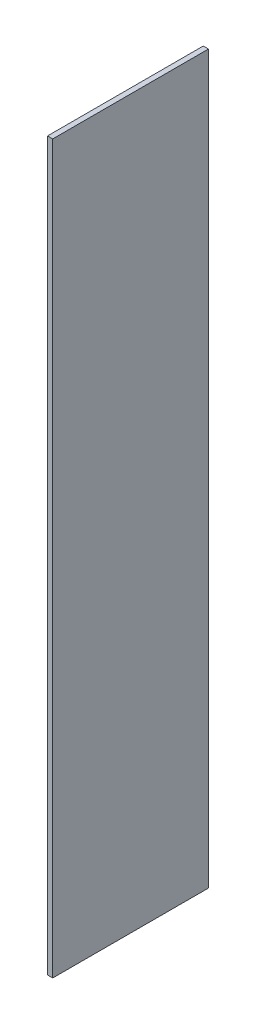
SolidWorks part; units mm, degrees
ref_plane "Front Plane" through (0, 0, 0) normal (0, 0, 1) x (1, 0, 0)
ref_plane "Top Plane" through (0, 0, 0) normal (0, 1, 0) x (1, 0, 0)
ref_plane "Right Plane" through (0, 0, 0) normal (1, 0, 0) x (0, 0, -1)
sketch "Sketch1" plane through (0, 0, 0) normal (0, 0, 1) x (1, 0, 0)
  line L1 (0, 0) -> (0.1, 0)
  line L2 (0, 0) -> (0, 14)
  line L3 (0, 14) -> (0.1, 14)
  line L4 (0.1, 0) -> (0.1, 14)
  dimension "D2" = 0.1
extrude "Boss-Extrude1" add sketch "Sketch1" along normal blind 3
equation "\"A.L\"= 0.06m"
equation "\"A.h\"= 0.005m"
equation "\"A.d\"= 0.003m"
equation "\"A.delta\"= 45.0001"
equation "\"A.w\"= 0.02m"
equation "\"A.v\"= 0.03m"
equation "\"A.s\"= 0.0075m"
equation "\"A.t\"= 0.005m"
equation "\"B.L\"= 0.04m"
equation "\"B.h\"= 0.004m"
equation "\"B.s\"= 0.008m"
equation "\"B.t\"= 0.004m"
equation "\"C.h\"= 0.0062m"
equation "\"C.d\"= 0.003m"
equation "\"C.L\"= 0.05m"
equation "\"C.wmax\"= 0.005m"
equation "\"D.L\"= 0.045m"
equation "\"D.h\"= 0.004m"
equation "\"D.s\"= 0.01m"
equation "\"D.t\"= 0.004m"
equation "\"a_h\"= 0.0001m"
equation "\"a_d\"= 0.003m"
equation "\"a_L\"= 0.01m"
equation "\"b_h\"= 0.0004m"
equation "\"b_d\"= 0.003m"
equation "\"b_L\"= 0.01m"
equation "\"c_h\"= 0.0001m"
equation "\"c_d\"= 0.003m"
equation "\"c_L\"= 0.01m"
equation "\"d_h\"= 0.0001m"
equation "\"d_d\"= 0.003m"
equation "\"d_L\"= 0.01m"
equation "\"S.h\"= 0.015m"
equation "\"S.L\"= 0.0559m"
equation "\"D1@Sketch1\"=\"c_L\"+0.004"
equation "\"D2@Sketch1\"=\"c_h\""
equation "\"D1@Boss-Extrude1\"=\"c_d\""
